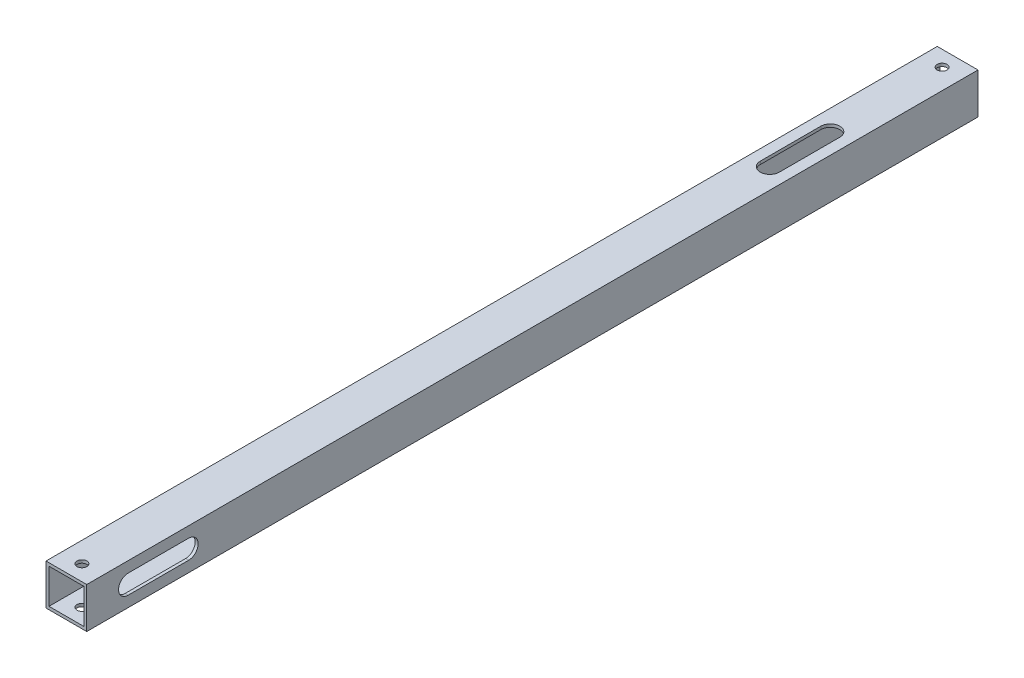
SolidWorks part; units mm, degrees
material "Aleación 1060"
ref_plane "Alzado" through (0, 0, 0) normal (0, 0, 1) x (1, 0, 0)
ref_plane "Planta" through (0, 0, 0) normal (0, 1, 0) x (1, 0, 0)
ref_plane "Vista lateral" through (0, 0, 0) normal (1, 0, 0) x (0, 0, -1)
sketch "Croquis1" plane through (0, 0, 0) normal (0, 0, 1) x (1, 0, 0)
  line L1 (-6.4, -6.4) -> (6.4, -6.4)
  line L2 (-6.4, -6.4) -> (-6.4, 6.4)
  line L3 (-6.4, 6.4) -> (6.4, 6.4)
  line L4 (6.4, -6.4) -> (6.4, 6.4)
  line L5 (-6.4, -6.4) -> (6.4, 6.4) construction
  line L6 (-6.4, 6.4) -> (6.4, -6.4) construction
  point P0 (0, 0)
  dimension "D1" = 12.8
extrude "Extruir-Lámina1" add sketch "Croquis1" against normal blind 280 thin thin type one direction reverse wall 0.94
sketch "Croquis2" plane through (0, 0, 0) normal (0, 1, 0) x (1, 0, 0)
  line L0 (6.4, 0) -> (-6.4, 0) construction
  line L1 (0, 240) -> (0, 221) construction
  line L2 (6.4, 280) -> (6.4, 0) construction
  line L3 (0, 0) -> (0, 280) construction
  line L4 (6.4, 280) -> (-6.4, 280) construction
  line L5 (-6.4, 140) -> (6.4, 140) construction
  line L6 (3, 240) -> (3, 221)
  line L7 (-3, 240) -> (-3, 221)
  circle A0 centre (0, 4.89) radius 1.55
  circle A1 centre (0, 275.11) radius 1.55
  arc A2 (3, 240) -> (-3, 240) centre (0, 240) ccw
  arc A3 (-3, 221) -> (3, 221) centre (0, 221) ccw
  point P14 (0, 140)
  point P18 (0, 230.5)
  point P23 (0, 243)
  point P24 (0, 0)
  point P25 (0, 0)
  dimension "D1" = 3.1
  dimension "D2" = 4.89
  dimension "D3" = 6.4
  dimension "D4" = 6
  dimension "D5" = 25
  dimension "D6" = 37
extrude "Cortar-Extruir1" cut sketch "Croquis2" along normal blind 10 and the other way blind 10 contours A1 | A0 region at (0, 0, -275.11)
extrude "Cortar-Extruir2" cut sketch "Croquis2<3>" along normal blind 10 contours L7 A3 L6 A2
sketch "Croquis2<3>" plane through (0, 0, 0) normal (0, 1, 0) x (1, 0, 0) same geometry as "Croquis2"
sketch "Croquis3" plane through (6.4, 0, 0) normal (1, 0, 0) x (0, 0, -1)
  line L0 (13, 0) -> (32, 0) construction
  line L2 (13, 3) -> (32, 3)
  line L3 (13, -3) -> (32, -3)
  arc A0 (13, 3) -> (13, -3) centre (13, 0) ccw
  arc A1 (32, -3) -> (32, 3) centre (32, 0) ccw
  point P3 (10, 0)
  point P5 (22.5, 0)
  dimension "D1" = 6
  dimension "D2" = 25
  dimension "D3" = 10
extrude "Cortar-Extruir5" cut sketch "Croquis3" against normal blind 10
